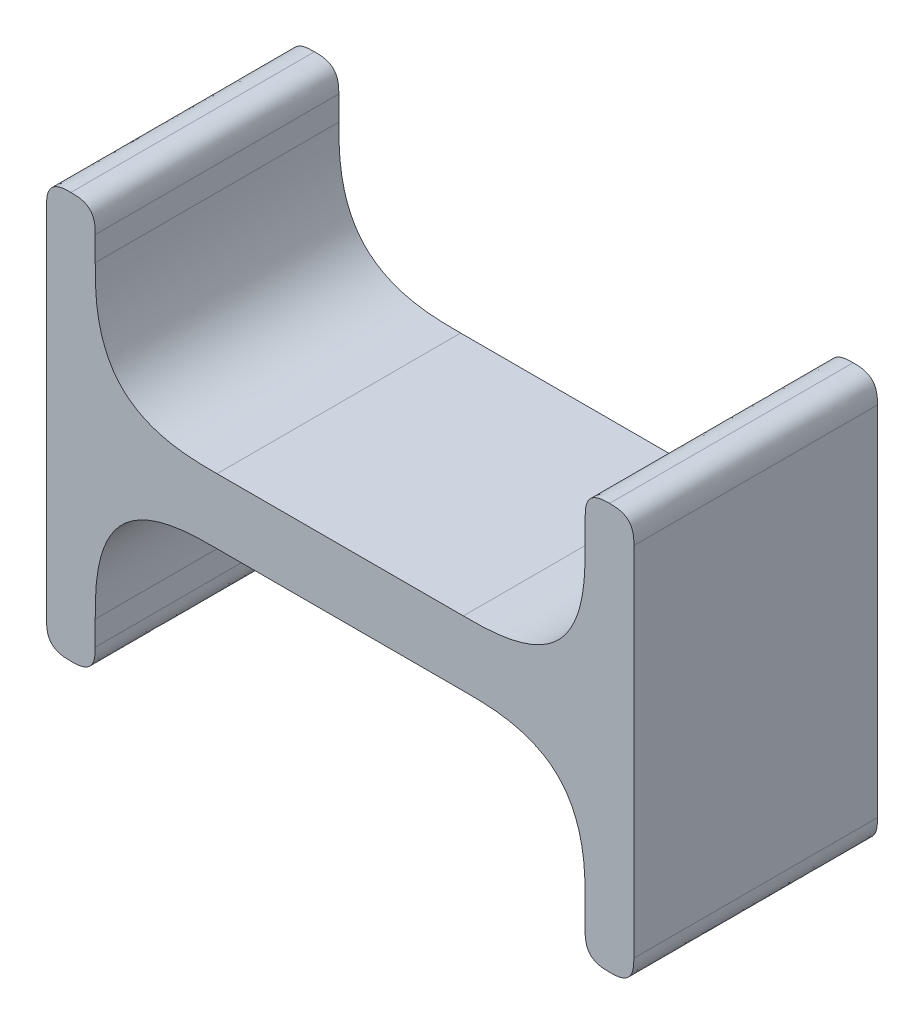
SolidWorks part; units mm, degrees
ref_plane "Front Plane" through (0, 0, 0) normal (0, 0, 1) x (1, 0, 0)
ref_plane "Top Plane" through (0, 0, 0) normal (0, 1, 0) x (1, 0, 0)
ref_plane "Right Plane" through (0, 0, 0) normal (1, 0, 0) x (0, 0, -1)
sketch "Sketch1" plane through (0, 0, 0) normal (0, 0, 1) x (1, 0, 0)
  line L0 (36.165, 0) -> (-36.165, 0)
  line L1 (-36.165, 25) -> (-36.165, -25)
  line L2 (0, 38.8839) -> (0, -37.2652) construction
  line L3 (36.165, 25) -> (36.165, -25)
  line L4 (30.165, -25) -> (36.165, -25)
  line L5 (-30.165, -25) -> (-36.165, -25)
  line L6 (-30.165, -25) -> (-30.165, 25)
  line L7 (-30.165, 25) -> (-36.165, 25)
  line L8 (-36.165, -25) -> (-36.165, 25)
  line L9 (-30.165, -25) -> (-36.165, 25) construction
  line L10 (-30.165, 25) -> (-36.165, -25) construction
  line L11 (30.165, -4) -> (-30.165, -4)
  line L12 (30.165, -4) -> (30.165, 4)
  line L13 (30.165, 4) -> (-30.165, 4)
  line L14 (-30.165, -4) -> (-30.165, 4)
  line L15 (30.165, -4) -> (-30.165, 4) construction
  line L16 (30.165, 4) -> (-30.165, -4) construction
  line L17 (36.165, 25) -> (36.165, -25)
  line L18 (30.165, 25) -> (36.165, 25)
  line L19 (30.165, -25) -> (30.165, 25)
  point P4 (0, 0)
  point P8 (-36.165, 0)
  point P12 (-33.165, 0)
  point P13 (0, 0)
  dimension "D1" = 72.33
  dimension "D2" = 50
  dimension "D3" = 6
  dimension "D4" = 8
extrude "Boss-Extrude1" add sketch "Sketch1" along normal blind 30 contours L6 L7 L1 L0 | L5 L6 L0 L1 | L11 L12 L0 L6 | L12 L13 L6 L0 | L19 L12 L0 L3 L18 | L19 L4 L3 L0 L12 region at (33.165, -12.5, 0) region at (33.165, 12.5, 0) region at (0, -2, 0) region at (0, 2, 0) region at (-33.165, -12.5, 0) region at (-33.165, 12.5, 0)
fillet "Fillet1" radius 15 4 edges at (30.165, -4, 15) (30.165, 4, 15) (-30.165, -4, 15) (-30.165, 4, 15) curvature continuous yes
fillet "Fillet2" radius 3 8 edges at (30.165, 25, 15) (36.165, 25, 15) (36.165, -25, 15) (30.165, -25, 15) (-30.165, -25, 15) (-36.165, -25, 15) (-36.165, 25, 15) (-30.165, 25, 15) curvature continuous yes
